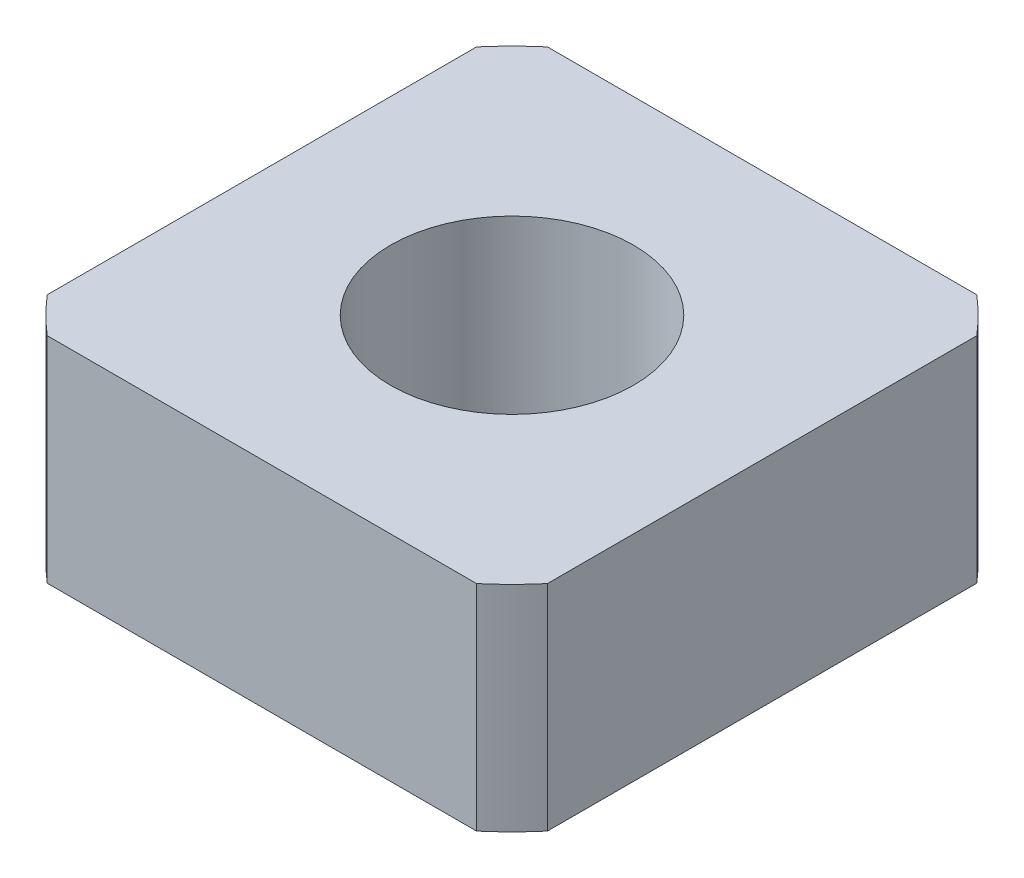
SolidWorks part; units mm, degrees
ref_plane "Front" through (0, 0, 0) normal (0, 0, 1) x (1, 0, 0)
ref_plane "Top" through (0, 0, 0) normal (0, 1, 0) x (1, 0, 0)
ref_plane "Right" through (0, 0, 0) normal (1, 0, 0) x (0, 0, -1)
sketch "Sketch1" plane through (0, 0, 0) normal (0, 1, 0) x (1, 0, 0)
  line L0 (0, 0) -> (-3.5, 0)
  line L1 (-3.5, 0) -> (-3.5, 3.5)
  line L2 (0, 0) -> (3.5, 0)
  line L3 (3.5, 0) -> (3.5, 3.5)
  line L4 (3.5, 3.5) -> (-3.5, 3.5)
  line L5 (-3.5, 0) -> (-3.5, -3.5)
  line L6 (-3.5, -3.5) -> (3.5, -3.5)
  line L7 (3.5, -3.5) -> (3.5, 0)
  circle A0 centre (0, 0) radius 4.6127
  circle A1 centre (0, 0) radius 1.7
  dimension "D1" = 3.5
  dimension "D2" = 3.5
  dimension "D3" = 3.5
  dimension "D4" = 3.5
extrude "Boss-Extrude1" add sketch "Sketch1" along normal blind 3 contours A1 L0 L5 A0 L6 L7 L2 | A1 L2 L3 A0 L4 L1 L0 region at (0, 0, 1.9679) region at (0, 0, -1.9679)
